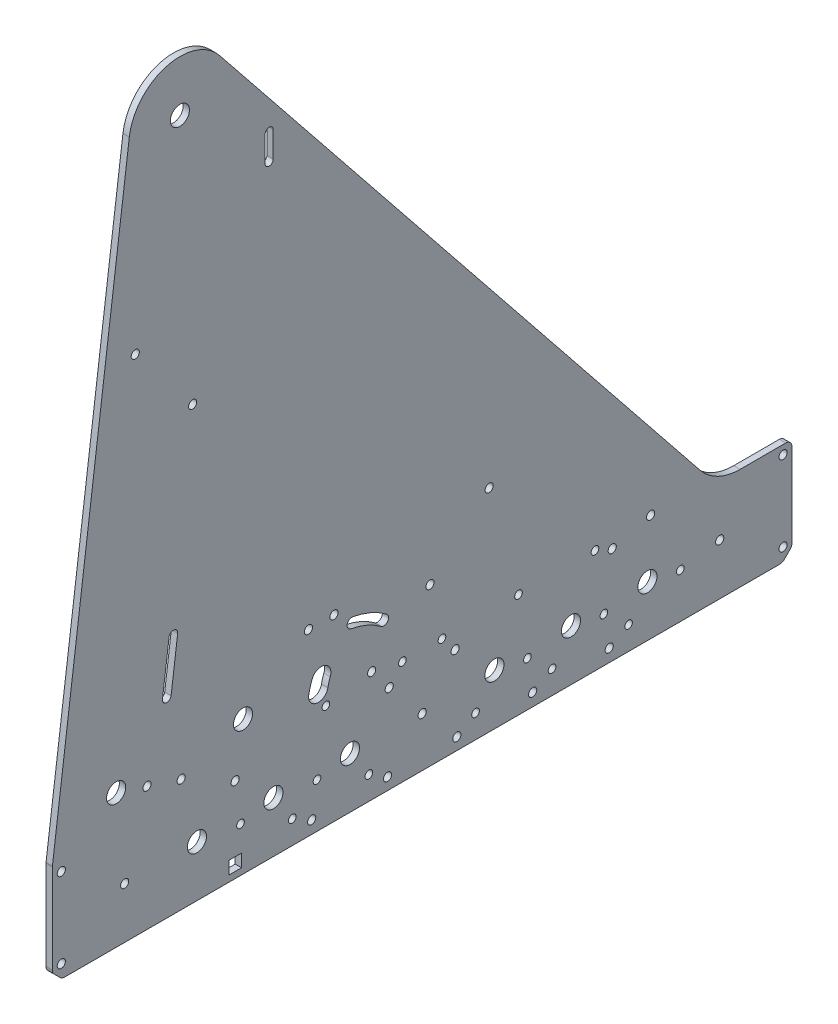
SolidWorks part; units mm, degrees
ref_plane "Front Plane" through (0, 0, 0) normal (0, 0, 1) x (1, 0, 0)
ref_plane "Top Plane" through (0, 0, 0) normal (0, 1, 0) x (1, 0, 0)
ref_plane "Right Plane" through (0, 0, 0) normal (1, 0, 0) x (0, 0, -1)
sketch "Sketch1" plane through (0, 0, 0) normal (1, 0, 0) x (0, 0, -1)
  line L0 (-184.15, -24.6062) -> (184.15, -24.6062)
  line L1 (184.15, -24.6062) -> (184.15, 26.1938)
  line L2 (184.15, 26.1938) -> (146.05, 26.1937)
  line L5 (-145.839, 321.5609) -> (-184.15, 26.1938)
  line L6 (-184.15, 26.1938) -> (-184.15, -24.6062)
  line L7 (-184.15, 350.0437) -> (184.15, 350.0437) construction
  line L9 (146.05, 26.1937) -> (-100.8314, 334.1803)
  arc A0 (-100.8314, 334.1803) -> (-145.839, 321.5609) centre (-120.65, 318.2937) ccw
  point P8 (0, -24.6062)
  dimension "D1" = 368.3
  dimension "D7" = 25.4
  dimension "D2" = 50.8
  dimension "D3" = 38.1
  dimension "D4" = 24.6062
  dimension "D5" = 374.65
  dimension "D6" = 304.8
  dimension "D8" = 342.9
extrude "Boss-Extrude1" add sketch "Sketch1" along normal blind 3.175
chamfer "Chamfer1" distance 4.7625 angle 45 2 edges at (1.5875, -24.6062, 184.15) (1.5875, -24.6062, -184.15)
fillet "Fillet1" radius 25.4 1 edges at (1.5875, 26.1937, -146.05)
fillet "Fillet2" radius 3.175 2 edges at (1.5875, 26.1938, 184.15) (1.5875, 26.1938, -184.15)
fillet "Fillet3" radius 3.175 4 edges at (1.5875, -19.8438, -184.15) (1.5875, -24.6062, -179.3875) (1.5875, -19.8437, 184.15) (1.5875, -24.6062, 179.3875)
sketch "Sketch30" plane through (3.175, 0, 0) normal (1, 0, 0) x (0, 0, -1)
  circle A8 centre (-89.211, 42.2593) radius 4.7625
  circle A9 centre (-25.1593, 30.6938) radius 2.032
  arc A10 (-51.7173, 35.4892) -> (-50.2741, 40.5715) centre (-25.1593, 30.6938) cw construction
  arc A11 (-54.7652, 42.3379) -> (-56.4665, 36.3468) centre (-25.1593, 30.6938) ccw
  arc A12 (-45.783, 38.8051) -> (-46.9681, 34.6317) centre (-25.1593, 30.6938) ccw
  arc A13 (-45.783, 38.8051) -> (-54.7652, 42.3379) centre (-50.2741, 40.5715) ccw
  arc A14 (-56.4665, 36.3468) -> (-46.9681, 34.6317) centre (-51.7173, 35.4892) ccw
  arc A15 (-34.9881, 56.6661) -> (-19.1131, 49.8125) centre (-41.7582, 19.1724) cw construction
  arc A16 (-17.6789, 51.753) -> (-34.5594, 59.0407) centre (-41.7582, 19.1724) ccw
  arc A17 (-20.5473, 47.8719) -> (-35.4169, 54.2915) centre (-41.7582, 19.1724) ccw
  arc A18 (-20.5473, 47.8719) -> (-17.6789, 51.753) centre (-19.1131, 49.8125) ccw
  arc A19 (-34.5594, 59.0407) -> (-35.4169, 54.2915) centre (-34.9881, 56.6661) ccw
  arc A20 (-19.1131, 49.8125) -> (-34.9881, 56.6661) centre (-41.7582, 19.1724) ccw construction
  circle A21 centre (94.6345, 23.8125) radius 2.032
  circle A22 centre (-56.6241, 64.5541) radius 2.032
  circle A23 centre (-43.9241, 64.5541) radius 2.032
  circle A24 centre (-56.6241, 64.5541) radius 1.905 construction
  circle A25 centre (-43.9241, 64.5541) radius 1.905 construction
  point P7 (-51.1204, 38.0658)
  point P19 (-26.6567, 54.1518)
  dimension "D2" = 9.652
  dimension "D4" = 4.064
  dimension "D1" = 4.064
  dimension ".375" = 9.525
  dimension "D3" = 4.826
extrude "Cut-Extrude9" cut sketch "Sketch30" against normal through all
sketch "Sketch16" plane through (3.175, 0, 0) normal (1, 0, 0) x (0, 0, -1)
  circle A0 centre (112.1746, 0.7937) radius 4.7625
  circle A1 centre (74.0746, 0.7937) radius 4.7625
  circle A2 centre (35.9746, 0.7937) radius 4.7625
  circle A3 centre (-35.9746, 0.7938) radius 4.7625
  circle A4 centre (-74.0746, 0.7938) radius 4.7625
  circle A5 centre (-112.1746, 0.7937) radius 4.7625
  dimension "D1" = 9.525
  dimension "D2" = 9.525
extrude "Cut-Extrude1" cut sketch "Sketch16" against normal up to next
sketch "Sketch25" plane through (3.175, 0, 0) normal (1, 0, 0) x (0, 0, -1)
  circle A0 centre (102.7672, -13.0003) radius 1.905 construction
  circle A1 centre (86.0486, 27.3622) radius 1.905 construction
  circle A2 centre (128.5804, -2.3081) radius 1.905 construction
  circle A3 centre (102.7672, -13.0003) radius 1.905
  circle A4 centre (86.0486, 27.3622) radius 1.905
  circle A5 centre (128.5804, -2.3081) radius 1.905
  circle A6 centre (64.6672, -13.0003) radius 1.905 construction
  circle A8 centre (-9.8486, 27.3622) radius 1.905 construction
  circle A10 centre (-47.9486, 27.3622) radius 1.905 construction
  circle A11 centre (-90.4804, -2.3081) radius 1.905 construction
  circle A12 centre (-64.6672, -13.0003) radius 1.905 construction
  circle A14 centre (-52.3804, -2.3081) radius 1.905 construction
  circle A15 centre (-26.5672, -13.0003) radius 1.905 construction
  circle A16 centre (9.8486, 27.3622) radius 1.905 construction
  circle A17 centre (26.5672, -13.0003) radius 1.905 construction
  circle A18 centre (47.9486, 27.3622) radius 1.905 construction
  circle A19 centre (52.3804, -2.3081) radius 1.905 construction
  circle A20 centre (90.4804, -2.3081) radius 1.905 construction
  circle A21 centre (-9.8486, 27.3622) radius 1.905
  circle A23 centre (-47.9486, 27.3622) radius 1.905
  circle A24 centre (-90.4804, -2.3081) radius 1.905
  circle A25 centre (-64.6672, -13.0003) radius 1.905
  circle A27 centre (-52.3804, -2.3081) radius 1.905
  circle A28 centre (-26.5672, -13.0003) radius 1.905
  circle A29 centre (9.8486, 27.3622) radius 1.905
  circle A30 centre (26.5672, -13.0003) radius 1.905
  circle A31 centre (47.9486, 27.3622) radius 1.905
  circle A32 centre (64.6672, -13.0003) radius 1.905
  circle A33 centre (52.3804, -2.3081) radius 1.905
  circle A34 centre (90.4804, -2.3081) radius 1.905
extrude "Cut-Extrude4" cut sketch "Sketch25" against normal up to next
sketch "Sketch23" plane through (3.175, 0, 0) normal (1, 0, 0) x (0, 0, -1)
  circle A0 centre (179.705, 21.7488) radius 1.905 construction
  point P0 (-55.0246, -18.3223)
  point P6 (-93.1246, 17.5943)
  point P9 (-17.2515, -18.6426)
  point P12 (-16.4124, 19.3854)
  point P15 (16.4124, 19.3854)
  point P18 (17.2515, -18.6426)
  point P21 (55.0246, -18.3223)
  point P35 (3.8736, 53.6853)
  point P38 (113.7728, 28.6594)
  point P41 (-137.0088, 37.226)
  point P44 (-179.705, 21.7487)
  point P47 (-179.705, -18.0026)
  point P50 (179.705, 21.7488)
  point P53 (179.705, -18.0026)
  point P59 (93.1246, -18.3223)
hole_wizard "#8 (0.16) Diameter Hole1" positions "Sketch23" profile "Sketch24" hole size "#8" standard "ANSI Inch" end condition up to next
sketch "Sketch24" plane through (3.175, -18.3223, 55.0246) normal (0, 1, 0) x (0, 0, -1)
  line L0 (0, 0) -> (0, 3.175)
  line L1 (0, 3.175) -> (2.032, 3.175)
  line L2 (2.032, 3.175) -> (2.032, 0)
  line L5 (2.032, 0) -> (0, 0)
  line L11 (0, -6.35) -> (0, 107.95) construction
  dimension "Thru Hole Dia." = 4.064
  dimension "Thru Hole Depth" = 3.175
sketch "Sketch22" plane through (3.175, 0, 0) normal (1, 0, 0) x (0, 0, -1)
  line L0 (-96.2996, -15.1473) -> (-89.9496, -15.1473) construction
  line L1 (-96.2996, -15.1473) -> (-89.9496, -15.1473)
  line L2 (-96.2996, -15.1473) -> (-96.2996, -21.4973)
  line L3 (-96.2996, -21.4973) -> (-89.9496, -21.4973)
  line L4 (-89.9496, -15.1473) -> (-89.9496, -21.4973)
  line L5 (-96.2996, -15.1473) -> (-89.9496, -21.4973) construction
  line L6 (-96.2996, -21.4973) -> (-89.9496, -15.1473) construction
  line L7 (-89.9496, -15.1473) -> (-89.9496, -19.8734) construction
  point P0 (-93.1246, -18.3223)
  dimension "D1" = 6.35
extrude "Cut-Extrude3" cut sketch "Sketch22" against normal up to next
sketch "Sketch21" plane through (3.175, 0, 0) normal (1, 0, 0) x (0, 0, -1)
  circle A0 centre (-148.1579, 0.7937) radius 2.032
  circle A2 centre (0, 0) radius 2.032
  circle A3 centre (148.1579, 0.7938) radius 2.032
  dimension "D1" = 4.064
extrude "Cut-Extrude2" cut sketch "Sketch21" against normal up to next
sketch "Sketch26" [suppressed] plane through (3.175, 0, 0) normal (1, 0, 0) x (0, 0, -1)
  line L0 (-145.839, 321.5609) -> (-184.1236, 26.3971) construction
  line L1 (-178.0724, -24.6062) -> (178.0724, -24.6062) construction
  circle A0 centre (-121.0218, 216.6937) radius 15.24
  dimension "D1" = 30.48
  dimension "D2" = 38.1
  dimension "D3" = 241.3
extrude "Cut-Extrude5" [suppressed] cut sketch "Sketch26" against normal through all
sketch "Sketch27" plane through (3.175, 0, 0) normal (1, 0, 0) x (0, 0, -1)
  circle A0 centre (-120.65, 318.2937) radius 4.7625
  dimension "D1" = 9.525
extrude "Cut-Extrude6" cut sketch "Sketch27" against normal through all
sketch "Sketch28" plane through (3.175, 0, 0) normal (1, 0, 0) x (0, 0, -1)
  line L0 (-120.65, 318.2937) -> (-103.5612, 277.2599) construction
  line L1 (-103.5612, 277.2599) -> (-86.3654, 258.566) construction
  line L2 (-86.3654, 258.566) -> (-90.1612, 246.4465) construction
  line L3 (-90.1612, 246.4465) -> (-93.9569, 234.327) construction
  line L4 (-145.839, 321.5609) -> (-184.1236, 26.3971) construction
  circle A0 centre (-93.9569, 234.327) radius 2.032
  circle A1 centre (-90.1612, 246.4465) radius 2.032
  circle A2 centre (-86.3654, 258.566) radius 2.0955
  circle A3 centre (-103.5612, 277.2599) radius 2.032
  dimension "D4" = 4.064
  dimension "D5" = 4.191
  dimension "D6" = 4.064
  dimension "D1" = 25.4
  dimension "D2" = 44.45
  dimension "D3" = 12.7
  dimension "D7" = 30
  dimension "D8" = 120
  dimension "D9" = 160
extrude "Cut-Extrude7" [suppressed] cut sketch "Sketch28" against normal through all
sketch "Sketch29" plane through (3.175, 0, 0) normal (1, 0, 0) x (0, 0, -1)
  line L1 (-76.2, 288.925) -> (-76.2, 276.225) construction
  line L2 (-74.168, 288.925) -> (-74.168, 276.225)
  line L3 (-78.232, 288.925) -> (-78.232, 276.225)
  arc A4 (-74.168, 288.925) -> (-78.232, 288.925) centre (-76.2, 288.925) ccw
  arc A5 (-78.232, 276.225) -> (-74.168, 276.225) centre (-76.2, 276.225) ccw
  point P8 (-76.2, 282.575)
  dimension "D1" = 276.225
  dimension "D2" = 2.032
  dimension "D3" = 76.2
  dimension "D4" = 12.7
sketch "Sketch31" plane through (0, 0, 0) normal (-1, 0, 0) x (0, 0, 1)
  circle A1 centre (114.3, 190.5) radius 2.032
  dimension "D1" = 114.3
  dimension "D6" = 4.064
  dimension "D2" = 190.5
extrude "Cut-Extrude10" cut sketch "Sketch31" against normal through all
sketch "Sketch34" plane through (0, 0, 0) normal (-1, 0, 0) x (0, 0, 1)
  line L3 (123.9045, 95.7355) -> (127.1716, 70.5465) construction
  line L4 (126.0455, 96.0132) -> (129.3127, 70.8242)
  line L5 (121.7634, 95.4578) -> (125.0306, 70.2688)
  line L6 (145.839, 321.5609) -> (184.1236, 26.3971) construction
  arc A2 (126.0455, 96.0132) -> (121.7634, 95.4578) centre (123.9045, 95.7355) ccw
  arc A3 (125.0306, 70.2688) -> (129.3127, 70.8242) centre (127.1716, 70.5465) ccw
  point P9 (125.538, 83.141)
  point P18 (114.3, 190.5)
  dimension "D8" = 4.318
  dimension "D6" = 50.8
  dimension "D7" = 25.4
  dimension "D9" = 95.25
extrude "Cut-Extrude12" cut sketch "Sketch34" against normal through all
sketch "Sketch38" plane through (3.175, 0, 0) normal (1, 0, 0) x (0, 0, -1)
  line L0 (-184.15, 25.9887) -> (-184.15, -18.5286) construction
  line L1 (-178.0724, -24.6062) -> (178.0724, -24.6062) construction
  circle A0 centre (-152.4, 42.0688) radius 4.7625
  dimension "D1" = 31.75
  dimension "D3" = 9.525
  dimension "D2" = 66.675
extrude "Cut-Extrude14" cut sketch "Sketch38" against normal through all
sketch "Sketch37" plane through (3.175, 0, 0) normal (1, 0, 0) x (0, 0, -1)
  circle A0 centre (33.3375, 80.645) radius 2.032
  circle A8 centre (0, 0) radius 2.032 construction
  dimension "D1" = 4.064
  dimension "D2" = 33.3375
  dimension "D3" = 80.645
extrude "Cut-Extrude13" cut sketch "Sketch37" against normal through all
extrude "Cut-Extrude15" cut sketch "Sketch29" against normal through all
sketch "Sketch40" plane through (3.175, 0, 0) normal (1, 0, 0) x (0, 0, -1)
  circle A0 centre (-120.015, 31.75) radius 2.032
  dimension "D1" = 4.064
  dimension "D2" = 120.015
  dimension "D3" = 31.75
extrude "Cut-Extrude16" cut sketch "Sketch40" against normal through all
sketch "Sketch41" [suppressed] plane through (3.175, 0, 0) normal (1, 0, 0) x (0, 0, -1)
  line L0 (-120.65, 318.2937) -> (-98.425, 279.7989) construction
  line L1 (-98.425, 279.7989) -> (-77.6666, 265.1617) construction
  line L2 (-120.65, 318.2937) -> (-60.41, 318.2937) construction
  circle A0 centre (-120.65, 318.2937) radius 25.4 construction
  circle A1 centre (-98.425, 279.7989) radius 19.05 construction
  circle A2 centre (-77.6666, 265.1617) radius 6.35 construction
  circle A3 centre (-98.425, 279.7989) radius 2.032
  circle A4 centre (-77.6666, 265.1617) radius 2.032
  dimension "D1" = 50.8
  dimension "D2" = 38.1
  dimension "D3" = 12.7
  dimension "D4" = 4.064
  dimension "D5" = 60
extrude "Cut-Extrude17" [suppressed] cut sketch "Sketch41" against normal through all
sketch "Sketch43" plane through (3.175, 0, 0) normal (1, 0, 0) x (0, 0, -1)
  line L0 (-152.4, 200.025) -> (-123.6487, 200.025) construction
  line L1 (-115.9779, 252.0412) -> (-152.4, 200.025) construction
  circle A0 centre (-152.4, 200.025) radius 2.032
  arc A1 (-143.2813, 262.8669) -> (-96.4668, 230.087) centre (-152.4, 200.025) cw construction
  arc A2 (-92.2158, 232.3717) -> (-142.5883, 267.6428) centre (-152.4, 200.025) ccw
  arc A3 (-100.7177, 227.8023) -> (-143.9743, 258.0909) centre (-152.4, 200.025) ccw
  arc A4 (-100.7177, 227.8023) -> (-92.2158, 232.3717) centre (-96.4668, 230.087) ccw
  arc A5 (-142.5883, 267.6428) -> (-143.9743, 258.0909) centre (-143.2813, 262.8669) ccw
  point P6 (-115.9779, 252.0412)
  dimension "D1" = 4.064
  dimension "D4" = 4.826
  dimension "D2" = 200.025
  dimension "D3" = 152.4
  dimension "D5" = 63.5
  dimension "D6" = 57.15
  dimension "D7" = 55
extrude "Cut-Extrude19" [suppressed] cut sketch "Sketch43" against normal through all
sketch "Sketch44" plane through (3.175, 0, 0) normal (1, 0, 0) x (0, 0, -1)
  circle A0 centre (-142.875, 226.3775) radius 2.032
  dimension "D1" = 4.064
  dimension "D2" = 142.875
  dimension "D3" = 226.3775
extrude "Cut-Extrude20" cut sketch "Sketch44" against normal through all
sketch "Sketch50" [suppressed] plane through (0, 0, 0) normal (-1, 0, 0) x (0, 0, 1)
  line L0 (98.7055, 213.2489) -> (51.4524, 213.2489) construction
  line L1 (98.7055, 211.2169) -> (51.4524, 211.2169)
  line L2 (98.7055, 215.2809) -> (51.4524, 215.2809)
  arc A1 (98.7055, 211.2169) -> (98.7055, 215.2809) centre (98.7055, 213.2489) ccw
  arc A2 (51.4524, 215.2809) -> (51.4524, 211.2169) centre (51.4524, 213.2489) ccw
  point P3 (75.079, 213.2489)
  dimension "D1" = 2.032
  dimension "D2" = 98.7055
  dimension "D3" = 213.2489
  dimension "D4" = 47.253
extrude "Cut-Extrude22" [suppressed] cut sketch "Sketch50" against normal through all
sketch "Sketch51" [suppressed] plane through (3.175, 0, 0) normal (1, 0, 0) x (0, 0, -1)
  circle A0 centre (-111.125, 222.6469) radius 2.032
  circle A1 centre (-111.125, 190.8969) radius 2.032
  dimension "D1" = 222.6469
  dimension "D3" = 31.75
  dimension "D4" = 4.064
  dimension "D2" = 111.125
extrude "Cut-Extrude23" [suppressed] cut sketch "Sketch51" against normal through all
sketch "Sketch52" [suppressed] plane through (0, 0, 0) normal (-1, 0, 0) x (0, 0, 1)
  line L0 (145.839, 321.5609) -> (184.1236, 26.3971) construction
  line L1 (142.875, 226.3775) -> (141.2656, 258.0867) construction
  line L2 (114.6094, 240.8383) -> (142.875, 226.3775) construction
  arc A5 (141.2656, 258.0867) -> (114.6094, 240.8383) centre (142.875, 226.3775) ccw construction
  arc A6 (141.1626, 260.1161) -> (112.8004, 241.7638) centre (142.875, 226.3775) ccw
  arc A7 (141.3686, 256.0573) -> (116.4184, 239.9128) centre (142.875, 226.3775) ccw
  arc A8 (141.3686, 256.0573) -> (141.1626, 260.1161) centre (141.2656, 258.0867) ccw
  arc A9 (112.8004, 241.7638) -> (116.4184, 239.9128) centre (114.6094, 240.8383) ccw
  point P4 (125.6266, 253.0338)
  dimension "D1" = 31.75
  dimension "D2" = 2.032
  dimension "D3" = 12.7
  dimension "D4" = 60
extrude "Cut-Extrude24" [suppressed] cut sketch "Sketch52" against normal through all
sketch "Sketch53" [suppressed] plane through (3.175, 0, 0) normal (1, 0, 0) x (0, 0, -1)
  line L0 (-35.2284, 197.2663) -> (-35.2284, 135.876) construction
  line L1 (-33.1964, 197.2663) -> (-33.1964, 135.876)
  line L2 (-37.2604, 197.2663) -> (-37.2604, 135.876)
  arc A0 (-33.1964, 197.2663) -> (-37.2604, 197.2663) centre (-35.2284, 197.2663) ccw
  arc A1 (-37.2604, 135.876) -> (-33.1964, 135.876) centre (-35.2284, 135.876) ccw
  point P2 (-35.2284, 166.5712)
  dimension "D1" = 2.032
  dimension "D2" = 61.3903
  dimension "D3" = 197.2663
  dimension "D4" = 35.2284
extrude "Cut-Extrude25" [suppressed] cut sketch "Sketch53" against normal through all
